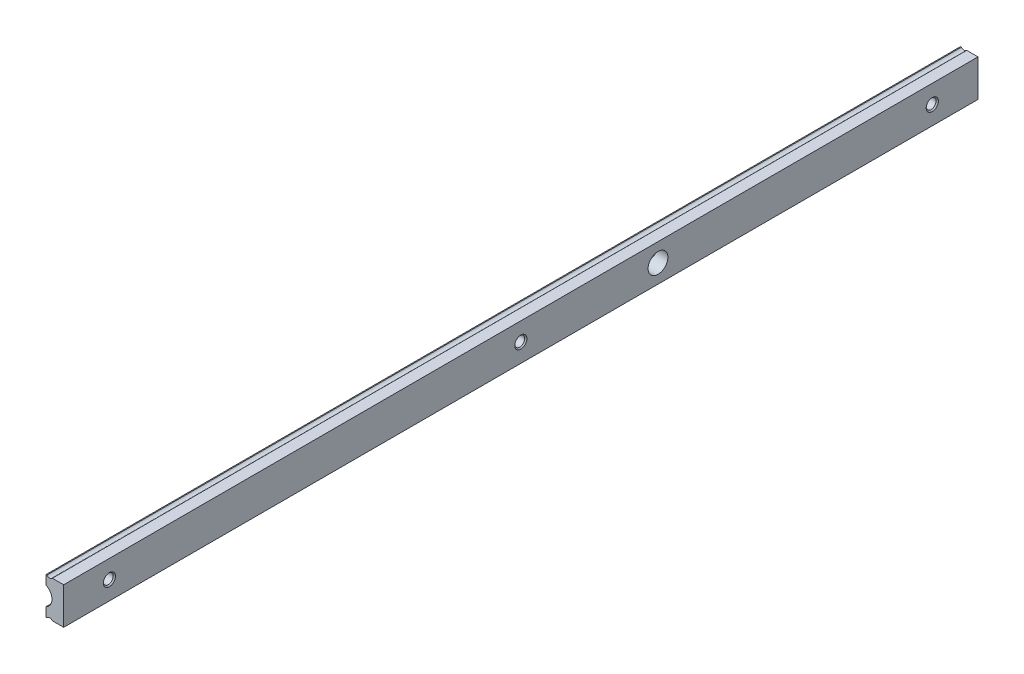
SolidWorks part; units mm, degrees
ref_plane "Front" through (0, 0, 0) normal (0, 0, 1) x (1, 0, 0)
ref_plane "Top" through (0, 0, 0) normal (0, 1, 0) x (1, 0, 0)
ref_plane "Right" through (0, 0, 0) normal (1, 0, 0) x (0, 0, -1)
ref_plane "Plane1" through (0, 0, 0) normal (0, 0, 1) x (1, 0, 0)
sketch "Sketch1" plane through (0, 0, 0) normal (0, 0, 1) x (1, 0, 0)
  line L0 (0, 2.9747) -> (0, 0)
  line L1 (0, 0) -> (0.3056, 0)
  line L2 (2.0944, 0) -> (5.8, 0)
  line L3 (5.8, 0) -> (5.8, 12.1)
  line L4 (5.8, 12.1) -> (2.0944, 12.1)
  line L5 (0.3056, 12.1) -> (0, 12.1)
  line L6 (0, 12.1) -> (0, 9.1253)
  arc A0 (0.3056, 0) -> (2.0944, 0) centre (1.2, -0.8) cw
  arc A1 (2.0944, 12.1) -> (0.3056, 12.1) centre (1.2, 12.9) cw
  arc A2 (0, 9.1253) -> (0, 2.9747) centre (-1.45, 6.05) cw
extrude "Boss-Extrude1" add sketch "Sketch1" along normal blind 300
ref_plane "Plane2" through (0, 0, 15) normal (0, 0, 1) x (1, 0, 0)
sketch "Sketch2" plane through (0, 0, 15) normal (0, 0, 1) x (1, 0, 0)
  line L0 (1.2995, 6.05) -> (1.2995, 8.05)
  line L1 (1.2995, 8.05) -> (1.6785, 7.671)
  line L2 (1.6785, 7.671) -> (5.421, 7.671)
  line L3 (5.421, 7.671) -> (5.8, 8.05)
  line L4 (5.8, 8.05) -> (5.8, 6.05)
  line L5 (5.8, 6.05) -> (1.2995, 6.05)
  line L6 (5.8, 6.05) -> (0, 6.05) construction
revolve "Cut-Revolve1" cut sketch "Sketch2" angle 360 about L6 reverse direction yes
cosmetic thread "Cosmetic Thread1" parameters "D1"=4.1215, "D2"=4
ref_plane "Plane3" through (0, 0, 285) normal (0, 0, 1) x (1, 0, 0)
sketch "Sketch3" plane through (0, 0, 285) normal (0, 0, 1) x (1, 0, 0)
  line L0 (1.2995, 6.05) -> (1.2995, 8.05)
  line L1 (1.2995, 8.05) -> (1.6785, 7.671)
  line L2 (1.6785, 7.671) -> (5.421, 7.671)
  line L3 (5.421, 7.671) -> (5.8, 8.05)
  line L4 (5.8, 8.05) -> (5.8, 6.05)
  line L5 (5.8, 6.05) -> (1.2995, 6.05)
  line L6 (5.8, 6.05) -> (0, 6.05) construction
revolve "Cut-Revolve2" cut sketch "Sketch3" angle 360 about L6 reverse direction yes
cosmetic thread "Cosmetic Thread2" parameters "D1"=4.1215, "D2"=4
ref_plane "Plane4" through (0, 0, 150) normal (0, 0, 1) x (1, 0, 0)
sketch "Sketch4" plane through (0, 0, 150) normal (0, 0, 1) x (1, 0, 0)
  line L0 (1.2995, 6.05) -> (1.2995, 8.05)
  line L1 (1.2995, 8.05) -> (1.6785, 7.671)
  line L2 (1.6785, 7.671) -> (5.421, 7.671)
  line L3 (5.421, 7.671) -> (5.8, 8.05)
  line L4 (5.8, 8.05) -> (5.8, 6.05)
  line L5 (5.8, 6.05) -> (1.2995, 6.05)
  line L6 (5.8, 6.05) -> (0, 6.05) construction
revolve "Cut-Revolve3" cut sketch "Sketch4" angle 360 about L6 reverse direction yes
cosmetic thread "Cosmetic Thread3" parameters "D1"=4.1215, "D2"=4
ref_plane "Plane5" through (5.8, 0, 0) normal (1, 0, 0) x (0, 0, -1)
sketch "Sketch5" plane through (5.8, 0, 0) normal (1, 0, 0) x (0, 0, -1)
  circle A0 centre (-105, 6.05) radius 3.25
extrude "Cut-Extrude1" cut sketch "Sketch5" against normal blind 6
